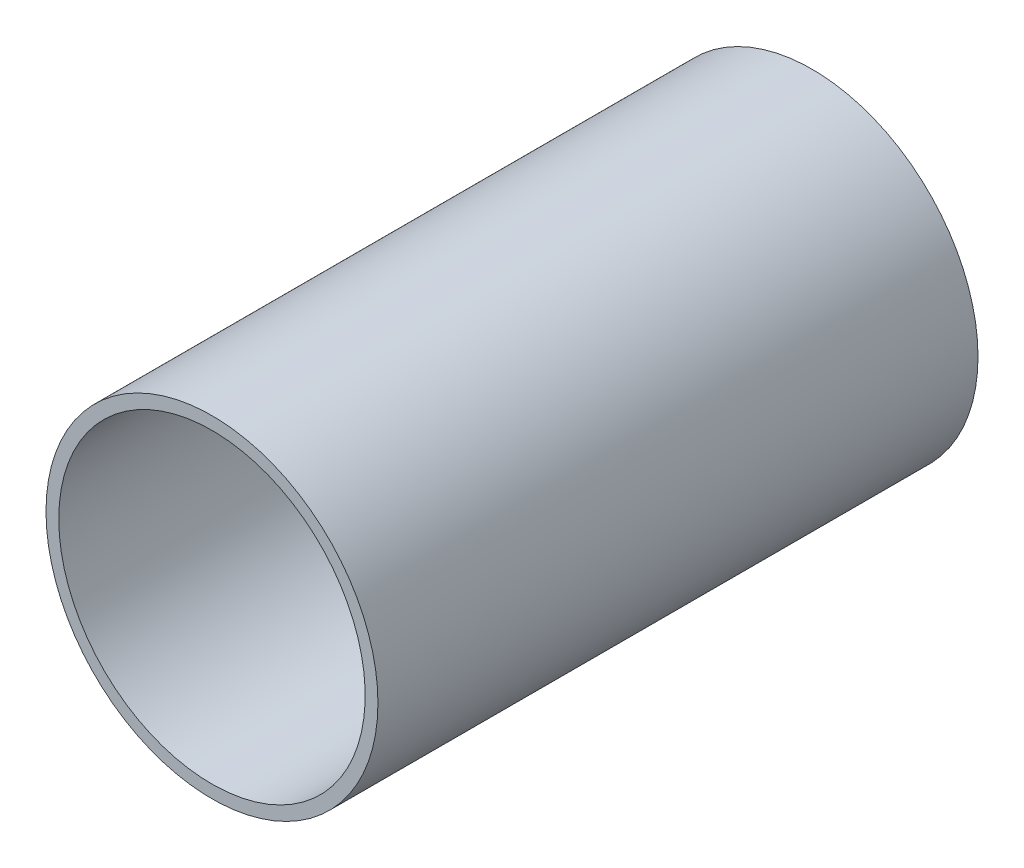
SolidWorks part; units mm, degrees
material "PMMA"
ref_plane "Plan de face" through (0, 0, 0) normal (0, 0, 1) x (1, 0, 0)
ref_plane "Plan de dessus" through (0, 0, 0) normal (0, 1, 0) x (1, 0, 0)
ref_plane "Plan de droite" through (0, 0, 0) normal (1, 0, 0) x (0, 0, -1)
ref_plane "Plan1" through (0, 0, 0) normal (0, -1, 0) x (1, 0, 0)
sketch "Esquisse1" plane through (0, 0, 0) normal (0, -1, 0) x (1, 0, 0)
  line L0 (82.55, -149.225) -> (82.55, 149.225)
  line L1 (82.55, 149.225) -> (76.2, 149.225)
  line L2 (76.2, 149.225) -> (76.2, -149.225)
  line L3 (76.2, -149.225) -> (82.55, -149.225)
  line L4 (0, 149.225) -> (0, -149.225) construction
revolve "Révolution1" add sketch "Esquisse1" angle 360 about L4 reverse direction yes
